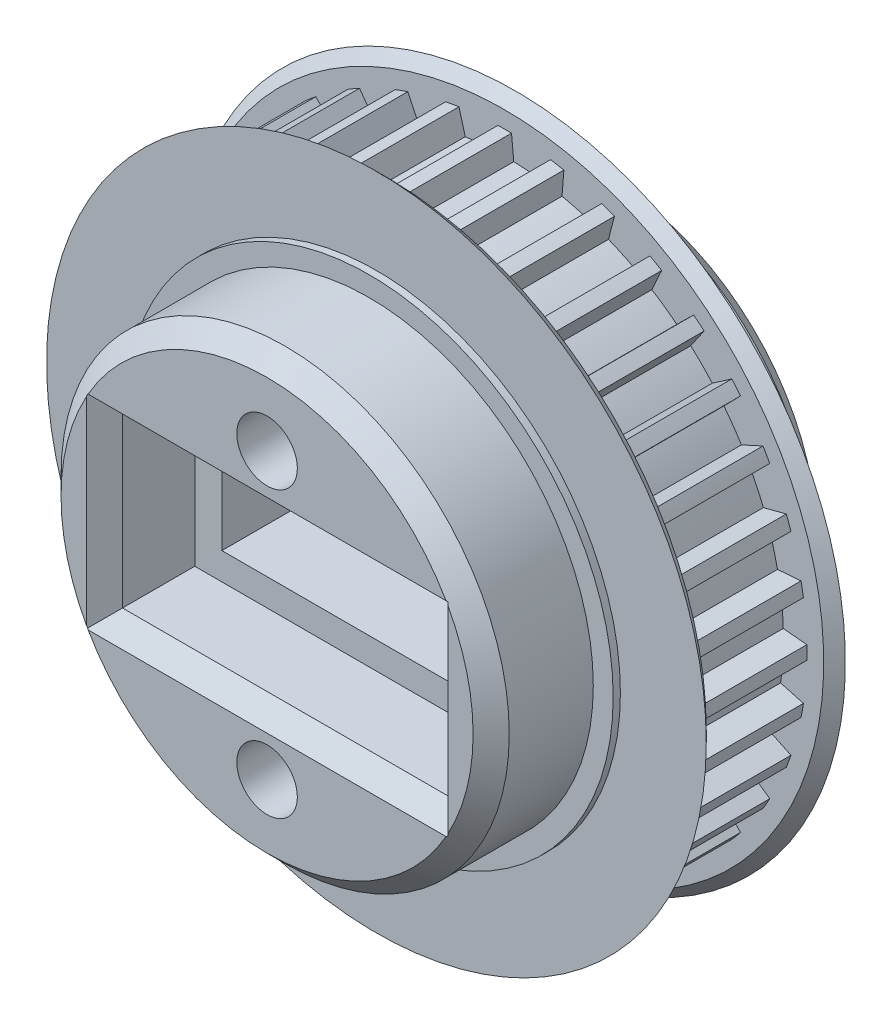
SolidWorks part; units mm, degrees
material "ABS"
ref_plane "Alzado" through (0, 0, 0) normal (0, 0, 1) x (1, 0, 0)
ref_plane "Planta" through (0, 0, 0) normal (0, 1, 0) x (1, 0, 0)
ref_plane "Vista lateral" through (0, 0, 0) normal (1, 0, 0) x (0, 0, -1)
sketch "Croquis1" plane through (0, 0, 0) normal (0, 0, 1) x (1, 0, 0)
  line L0 (0, 0) -> (0, 14.5885) construction
  line L1 (-0.375, 16.7142) -> (-0.5, 15.4103)
  line L2 (0.375, 16.7142) -> (0.5, 15.4103)
  line L3 (3.2717, 16.3952) -> (3.1684, 15.0894)
  line L4 (2.5331, 16.5254) -> (2.1836, 15.263)
  line L5 (6.069, 15.578) -> (5.7405, 14.3099)
  line L6 (5.3642, 15.8345) -> (4.8008, 14.652)
  line L7 (8.6819, 14.2874) -> (8.1382, 13.0957)
  line L8 (8.0323, 14.6624) -> (7.2721, 13.5957)
  line L9 (11.031, 12.5628) -> (10.2886, 11.4836)
  line L10 (10.4564, 13.0449) -> (9.5225, 12.1264)
  line L11 (13.0449, 10.4564) -> (12.1264, 9.5225)
  line L12 (12.5628, 11.031) -> (11.4836, 10.2886)
  line L13 (14.6624, 8.0323) -> (13.5957, 7.2721)
  line L14 (14.2874, 8.6819) -> (13.0957, 8.1382)
  line L15 (15.8345, 5.3642) -> (14.652, 4.8008)
  line L16 (15.578, 6.069) -> (14.3099, 5.7405)
  line L17 (16.5254, 2.5331) -> (15.263, 2.1836)
  line L18 (16.3952, 3.2717) -> (15.0894, 3.1684)
  line L19 (16.7142, -0.375) -> (15.4103, -0.5)
  line L20 (16.7142, 0.375) -> (15.4103, 0.5)
  line L21 (16.3952, -3.2717) -> (15.0894, -3.1684)
  line L22 (16.5254, -2.5331) -> (15.263, -2.1836)
  line L23 (15.578, -6.069) -> (14.3099, -5.7405)
  line L24 (15.8345, -5.3642) -> (14.652, -4.8008)
  line L25 (14.2874, -8.6819) -> (13.0957, -8.1382)
  line L26 (14.6624, -8.0323) -> (13.5957, -7.2721)
  line L27 (12.5628, -11.031) -> (11.4836, -10.2886)
  line L28 (13.0449, -10.4564) -> (12.1264, -9.5225)
  line L29 (10.4564, -13.0449) -> (9.5225, -12.1264)
  line L30 (11.031, -12.5628) -> (10.2886, -11.4836)
  line L31 (8.0323, -14.6624) -> (7.2721, -13.5957)
  line L32 (8.6819, -14.2874) -> (8.1382, -13.0957)
  line L33 (5.3642, -15.8345) -> (4.8008, -14.652)
  line L34 (6.069, -15.578) -> (5.7405, -14.3099)
  line L35 (2.5331, -16.5254) -> (2.1836, -15.263)
  line L36 (3.2717, -16.3952) -> (3.1684, -15.0894)
  line L37 (-0.375, -16.7142) -> (-0.5, -15.4103)
  line L38 (0.375, -16.7142) -> (0.5, -15.4103)
  line L39 (-3.2717, -16.3952) -> (-3.1684, -15.0894)
  line L40 (-2.5331, -16.5254) -> (-2.1836, -15.263)
  line L41 (-6.069, -15.578) -> (-5.7405, -14.3099)
  line L42 (-5.3642, -15.8345) -> (-4.8008, -14.652)
  line L43 (-8.6819, -14.2874) -> (-8.1382, -13.0957)
  line L44 (-8.0323, -14.6624) -> (-7.2721, -13.5957)
  line L45 (-11.031, -12.5628) -> (-10.2886, -11.4836)
  line L46 (-10.4564, -13.0449) -> (-9.5225, -12.1264)
  line L47 (-13.0449, -10.4564) -> (-12.1264, -9.5225)
  line L48 (-12.5628, -11.031) -> (-11.4836, -10.2886)
  line L49 (-14.6624, -8.0323) -> (-13.5957, -7.2721)
  line L50 (-14.2874, -8.6819) -> (-13.0957, -8.1382)
  line L51 (-15.8345, -5.3642) -> (-14.652, -4.8008)
  line L52 (-15.578, -6.069) -> (-14.3099, -5.7405)
  line L53 (-16.5254, -2.5331) -> (-15.263, -2.1836)
  line L54 (-16.3952, -3.2717) -> (-15.0894, -3.1684)
  line L55 (-16.7142, 0.375) -> (-15.4103, 0.5)
  line L56 (-16.7142, -0.375) -> (-15.4103, -0.5)
  line L57 (-16.3952, 3.2717) -> (-15.0894, 3.1684)
  line L58 (-16.5254, 2.5331) -> (-15.263, 2.1836)
  line L59 (-15.578, 6.069) -> (-14.3099, 5.7405)
  line L60 (-15.8345, 5.3642) -> (-14.652, 4.8008)
  line L61 (-14.2874, 8.6819) -> (-13.0957, 8.1382)
  line L62 (-14.6624, 8.0323) -> (-13.5957, 7.2721)
  line L63 (-12.5628, 11.031) -> (-11.4836, 10.2886)
  line L64 (-13.0449, 10.4564) -> (-12.1264, 9.5225)
  line L65 (-10.4564, 13.0449) -> (-9.5225, 12.1264)
  line L66 (-11.031, 12.5628) -> (-10.2886, 11.4836)
  line L67 (-8.0323, 14.6624) -> (-7.2721, 13.5957)
  line L68 (-8.6819, 14.2874) -> (-8.1382, 13.0957)
  line L69 (-5.3642, 15.8345) -> (-4.8008, 14.652)
  line L70 (-6.069, 15.578) -> (-5.7405, 14.3099)
  line L71 (-2.5331, 16.5254) -> (-2.1836, 15.263)
  line L72 (-3.2717, 16.3952) -> (-3.1684, 15.0894)
  arc A0 (-10.4564, 13.0449) -> (-11.031, 12.5628) centre (0, 0) ccw
  arc A1 (2.1836, 15.263) -> (0.5, 15.4103) centre (0, 0) ccw
  arc A2 (-12.5628, 11.031) -> (-13.0449, 10.4564) centre (0, 0) ccw
  arc A3 (-14.2874, 8.6819) -> (-14.6624, 8.0323) centre (0, 0) ccw
  arc A4 (-15.578, 6.069) -> (-15.8345, 5.3642) centre (0, 0) ccw
  arc A5 (-16.3952, 3.2717) -> (-16.5254, 2.5331) centre (0, 0) ccw
  arc A6 (-16.7142, 0.375) -> (-16.7142, -0.375) centre (0, 0) ccw
  arc A7 (-16.5254, -2.5331) -> (-16.3952, -3.2717) centre (0, 0) ccw
  arc A8 (-15.8345, -5.3642) -> (-15.578, -6.069) centre (0, 0) ccw
  arc A9 (-14.6624, -8.0323) -> (-14.2874, -8.6819) centre (0, 0) ccw
  arc A10 (-13.0449, -10.4564) -> (-12.5628, -11.031) centre (0, 0) ccw
  arc A11 (3.2717, 16.3952) -> (2.5331, 16.5254) centre (0, 0) ccw
  arc A12 (0.375, 16.7142) -> (-0.375, 16.7142) centre (0, 0) ccw
  arc A13 (-5.3642, 15.8345) -> (-6.069, 15.578) centre (0, 0) ccw
  arc A14 (-8.0323, 14.6624) -> (-8.6819, 14.2874) centre (0, 0) ccw
  arc A15 (-2.5331, 16.5254) -> (-3.2717, 16.3952) centre (0, 0) ccw
  arc A16 (6.069, 15.578) -> (5.3642, 15.8345) centre (0, 0) ccw
  arc A17 (8.6819, 14.2874) -> (8.0323, 14.6624) centre (0, 0) ccw
  arc A18 (11.031, 12.5628) -> (10.4564, 13.0449) centre (0, 0) ccw
  arc A19 (13.0449, 10.4564) -> (12.5628, 11.031) centre (0, 0) ccw
  arc A20 (14.6624, 8.0323) -> (14.2874, 8.6819) centre (0, 0) ccw
  arc A21 (15.8345, 5.3642) -> (15.578, 6.069) centre (0, 0) ccw
  arc A22 (16.5254, 2.5331) -> (16.3952, 3.2717) centre (0, 0) ccw
  arc A23 (16.7142, -0.375) -> (16.7142, 0.375) centre (0, 0) ccw
  arc A24 (16.3952, -3.2717) -> (16.5254, -2.5331) centre (0, 0) ccw
  arc A25 (15.578, -6.069) -> (15.8345, -5.3642) centre (0, 0) ccw
  arc A26 (8.0323, -14.6624) -> (8.6819, -14.2874) centre (0, 0) ccw
  arc A27 (5.3642, -15.8345) -> (6.069, -15.578) centre (0, 0) ccw
  arc A28 (2.5331, -16.5254) -> (3.2717, -16.3952) centre (0, 0) ccw
  arc A29 (-3.2717, -16.3952) -> (-2.5331, -16.5254) centre (0, 0) ccw
  arc A30 (-6.069, -15.578) -> (-5.3642, -15.8345) centre (0, 0) ccw
  arc A31 (-8.6819, -14.2874) -> (-8.0323, -14.6624) centre (0, 0) ccw
  arc A32 (-11.031, -12.5628) -> (-10.4564, -13.0449) centre (0, 0) ccw
  arc A33 (10.4564, -13.0449) -> (11.031, -12.5628) centre (0, 0) ccw
  arc A34 (12.5628, -11.031) -> (13.0449, -10.4564) centre (0, 0) ccw
  arc A35 (14.2874, -8.6819) -> (14.6624, -8.0323) centre (0, 0) ccw
  arc A36 (4.8008, 14.652) -> (3.1684, 15.0894) centre (0, 0) ccw
  arc A37 (7.2721, 13.5957) -> (5.7405, 14.3099) centre (0, 0) ccw
  arc A38 (-3.1684, 15.0894) -> (-4.8008, 14.652) centre (0, 0) ccw
  arc A39 (-0.5, 15.4103) -> (-2.1836, 15.263) centre (0, 0) ccw
  arc A40 (-5.7405, 14.3099) -> (-7.2721, 13.5957) centre (0, 0) ccw
  arc A41 (-8.1382, 13.0957) -> (-9.5225, 12.1264) centre (0, 0) ccw
  arc A42 (-10.2886, 11.4836) -> (-11.4836, 10.2886) centre (0, 0) ccw
  arc A43 (9.5225, 12.1264) -> (8.1382, 13.0957) centre (0, 0) ccw
  arc A44 (11.4836, 10.2886) -> (10.2886, 11.4836) centre (0, 0) ccw
  arc A45 (13.0957, 8.1382) -> (12.1264, 9.5225) centre (0, 0) ccw
  arc A46 (14.3099, 5.7405) -> (13.5957, 7.2721) centre (0, 0) ccw
  arc A47 (15.0894, 3.1684) -> (14.652, 4.8008) centre (0, 0) ccw
  arc A48 (15.4103, 0.5) -> (15.263, 2.1836) centre (0, 0) ccw
  arc A49 (15.263, -2.1836) -> (15.4103, -0.5) centre (0, 0) ccw
  arc A50 (14.652, -4.8008) -> (15.0894, -3.1684) centre (0, 0) ccw
  arc A51 (13.5957, -7.2721) -> (14.3099, -5.7405) centre (0, 0) ccw
  arc A52 (12.1264, -9.5225) -> (13.0957, -8.1382) centre (0, 0) ccw
  arc A53 (10.2886, -11.4836) -> (11.4836, -10.2886) centre (0, 0) ccw
  arc A54 (8.1382, -13.0957) -> (9.5225, -12.1264) centre (0, 0) ccw
  arc A55 (5.7405, -14.3099) -> (7.2721, -13.5957) centre (0, 0) ccw
  arc A56 (3.1684, -15.0894) -> (4.8008, -14.652) centre (0, 0) ccw
  arc A57 (0.5, -15.4103) -> (2.1836, -15.263) centre (0, 0) ccw
  arc A58 (-2.1836, -15.263) -> (-0.5, -15.4103) centre (0, 0) ccw
  arc A59 (-4.8008, -14.652) -> (-3.1684, -15.0894) centre (0, 0) ccw
  arc A60 (-7.2721, -13.5957) -> (-5.7405, -14.3099) centre (0, 0) ccw
  arc A61 (-9.5225, -12.1264) -> (-8.1382, -13.0957) centre (0, 0) ccw
  arc A62 (-11.4836, -10.2886) -> (-10.2886, -11.4836) centre (0, 0) ccw
  arc A63 (-13.0957, -8.1382) -> (-12.1264, -9.5225) centre (0, 0) ccw
  arc A64 (-14.3099, -5.7405) -> (-13.5957, -7.2721) centre (0, 0) ccw
  arc A65 (-15.0894, -3.1684) -> (-14.652, -4.8008) centre (0, 0) ccw
  arc A66 (-15.4103, -0.5) -> (-15.263, -2.1836) centre (0, 0) ccw
  arc A67 (-15.263, 2.1836) -> (-15.4103, 0.5) centre (0, 0) ccw
  arc A68 (-14.652, 4.8008) -> (-15.0894, 3.1684) centre (0, 0) ccw
  arc A69 (-13.5957, 7.2721) -> (-14.3099, 5.7405) centre (0, 0) ccw
  arc A70 (-12.1264, 9.5225) -> (-13.0957, 8.1382) centre (0, 0) ccw
  arc A71 (-0.375, -16.7142) -> (0.375, -16.7142) centre (0, 0) ccw
  circle A72 centre (0, 0) radius 2
  point P151 (0, 0)
  dimension "D1" = 1.3
  dimension "D6" = 4
  dimension "D2" = 1
  dimension "D3" = 0.75
  dimension "D5" = 1.69
  dimension "D4" = 36
extrude "Saliente-Extruir1" add sketch "Croquis1" along normal blind 6.5
sketch "Croquis2" plane through (0, 0, 6.5) normal (0, 0, 1) x (1, 0, 0)
  circle A0 centre (0, 0) radius 18.25
  circle A1 centre (0, 0) radius 2
  circle A2 centre (0, 0) radius 2 construction
  dimension "D1" = 36.5
extrude "Saliente-Extruir2" add sketch "Croquis2" along normal blind 0.6
sketch "Croquis3" plane through (0, 0, 7.1) normal (0, 0, 1) x (1, 0, 0)
  circle A0 centre (0, 0) radius 2
  circle A1 centre (0, 0) radius 12.4
  circle A3 centre (0, 0) radius 2 construction
  dimension "D1" = 24.8
sketch "Croquis4" plane through (0, 0, 0) normal (0, 0, -1) x (-1, 0, 0)
  circle A0 centre (0, 0) radius 2
  circle A1 centre (0, 0) radius 12.45
  circle A2 centre (0, 0) radius 2 construction
  dimension "D1" = 24.9
extrude "Saliente-Extruir4" add sketch "Croquis4" along normal blind 5.8
sketch "Croquis6" plane through (0, 0, 0) normal (0, 0, -1) x (-1, 0, 0)
  circle A0 centre (0, 0) radius 18.25
  circle A1 centre (0, 0) radius 2
  circle A2 centre (0, 0) radius 2 construction
  dimension "D1" = 36.5
extrude "Saliente-Extruir6" add sketch "Croquis6" along normal blind 0.6
sketch "Croquis5" plane through (0, 0, -0.6) normal (0, 0, -1) x (-1, 0, 0)
  circle A0 centre (0, 0) radius 2
  circle A1 centre (0, 0) radius 13.5
  circle A2 centre (0, 0) radius 2 construction
  dimension "D1" = 27
extrude "Saliente-Extruir5" add sketch "Croquis5" along normal blind 0.4
extrude "Saliente-Extruir7" add sketch "Croquis3" along normal blind 6.05
chamfer "Chaflán4" distance 1 angle 45 2 edges at (-12.45, 0, -5.8) (12.4, 0, 13.15)
sketch "Croquis7" plane through (0, 0, 7.1) normal (0, 0, 1) x (1, 0, 0)
  circle A0 centre (0, 0) radius 2
  circle A1 centre (0, 0) radius 13.5
  circle A2 centre (0, 0) radius 2 construction
  dimension "D1" = 27
extrude "Saliente-Extruir8" add sketch "Croquis7" along normal blind 0.4
sketch "Croquis8" plane through (0, 0, 0) normal (0, 0, 1) x (1, 0, 0)
  line L0 (0, 0) -> (6.706, 0) construction
  line L1 (-7.5, 3.15) -> (7.5, 3.15)
  line L2 (-7.5, 3.15) -> (-7.5, -3.15)
  line L3 (-7.5, -3.15) -> (7.5, -3.15)
  line L4 (7.5, 3.15) -> (7.5, -3.15)
  line L5 (-7.5, 3.15) -> (7.5, -3.15) construction
  line L6 (-7.5, -3.15) -> (7.5, 3.15) construction
  circle A0 centre (0, 7.8756) radius 1.675
  circle A1 centre (0, -7.8756) radius 1.675
  point P0 (0, 0)
  dimension "D1" = 3.35
  dimension "D2" = 6.3
  dimension "D3" = 15
extrude "Cortar-Extruir1" cut sketch "Croquis8" against normal through all both and the other way through all
sketch "Croquis9" plane through (0, 0, -5.8) normal (0, 0, -1) x (-1, 0, 0)
  line L1 (2.3383, 3.8256) -> (4.6765, 7.8756)
  line L2 (4.6765, 7.8756) -> (2.3383, 11.9256)
  line L3 (2.3383, 11.9256) -> (-2.3383, 11.9256)
  line L4 (-2.3383, 11.9256) -> (-4.6765, 7.8756)
  line L5 (-4.6765, 7.8756) -> (-2.3383, 3.8256)
  line L6 (-2.3383, 3.8256) -> (2.3383, 3.8256)
  line L7 (2.3383, -11.9256) -> (4.6765, -7.8756)
  line L8 (4.6765, -7.8756) -> (2.3383, -3.8256)
  line L9 (2.3383, -3.8256) -> (-2.3383, -3.8256)
  line L10 (-2.3383, -3.8256) -> (-4.6765, -7.8756)
  line L11 (-4.6765, -7.8756) -> (-2.3383, -11.9256)
  line L12 (-2.3383, -11.9256) -> (2.3383, -11.9256)
  circle A0 centre (0, 7.8756) radius 4.05 construction
  circle A1 centre (0, -7.8756) radius 4.05 construction
  dimension "D1" = 8.1
extrude "Cortar-Extruir2" cut sketch "Croquis9" against normal blind 7
fillet "Redondeo1" radius 2.5 12 edges at (3.5074, -9.9006, 1.2) (3.5074, -5.8506, 1.2) (0, -3.8256, 1.2) (-3.5074, -5.8506, 1.2) (0, -11.9256, 1.2) (-3.5074, -9.9006, 1.2) (-3.5074, 5.8506, 1.2) (-3.5074, 9.9006, 1.2) (0, 11.9256, 1.2) (3.5074, 9.9006, 1.2) (3.5074, 5.8506, 1.2) (0, 3.8256, 1.2)
sketch "Croquis10" plane through (0, 0, 13.15) normal (0, 0, 1) x (1, 0, 0)
  line L0 (7.5, 3.15) -> (-7.5, 3.15) construction
  line L1 (9, 4.65) -> (-9, 4.65)
  line L2 (9, 4.65) -> (9, -4.65)
  line L3 (9, -4.65) -> (-9, -4.65)
  line L4 (-9, 4.65) -> (-9, -4.65)
  line L5 (9, 4.65) -> (-9, -4.65) construction
  line L6 (9, -4.65) -> (-9, 4.65) construction
  line L7 (-7.5, 3.15) -> (-7.5, -3.15) construction
  point P0 (0, 0)
  dimension "D1" = 1.5
  dimension "D2" = 1.5
extrude "Cortar-Extruir3" cut sketch "Croquis10" against normal blind 5
chamfer "Chaflán5" distance 1 angle 45 8 edges at (-7.5, 0, -5.8) (0, 3.15, -5.8) (7.5, 0, -5.8) (0, -3.15, -5.8) (9, 0, 13.15) (0, 4.65, 13.15) (-9, 0, 13.15) (0, -4.65, 13.15)
chamfer "Chaflán6" distance 0.6 angle 45 2 edges at (18.25, 0, 6.5) (-18.25, 0, 0)
